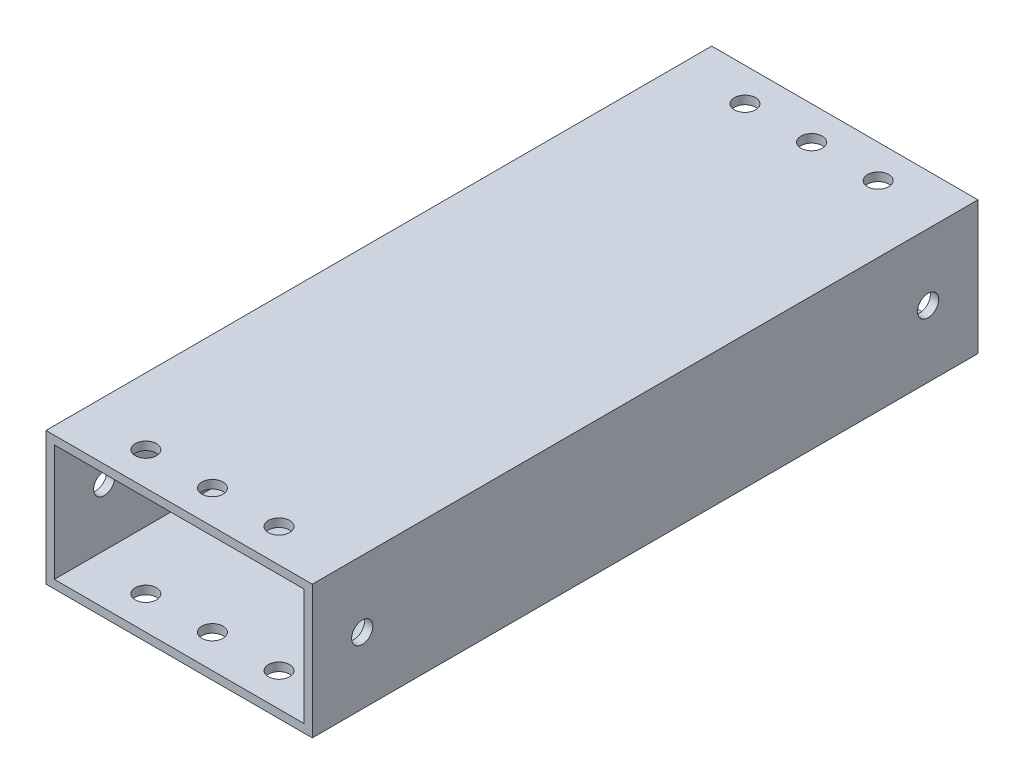
SolidWorks part; units mm, degrees
ref_plane "Front Plane" through (0, 0, 0) normal (0, 0, 1) x (1, 0, 0)
ref_plane "Top Plane" through (0, 0, 0) normal (0, 1, 0) x (1, 0, 0)
ref_plane "Right Plane" through (0, 0, 0) normal (1, 0, 0) x (0, 0, -1)
sketch "Sketch1" plane through (0, 0, 0) normal (0, 0, 1) x (1, 0, 0)
  line L0 (-23.8125, 11.1125) -> (23.8125, 11.1125)
  line L1 (-25.4, -12.7) -> (25.4, -12.7)
  line L2 (-25.4, -12.7) -> (-25.4, 12.7)
  line L3 (-25.4, 12.7) -> (25.4, 12.7)
  line L4 (25.4, -12.7) -> (25.4, 12.7)
  line L5 (-25.4, -12.7) -> (25.4, 12.7) construction
  line L6 (-25.4, 12.7) -> (25.4, -12.7) construction
  line L7 (23.8125, -11.1125) -> (23.8125, 11.1125)
  line L8 (-23.8125, -11.1125) -> (23.8125, -11.1125)
  line L9 (-23.8125, -11.1125) -> (-23.8125, 11.1125)
  point P0 (0, 0)
  dimension "D1" = 50.8
  dimension "D2" = 25.4
  dimension "D3" = 1.5875
extrude "Boss-Extrude1" add sketch "Sketch1" along normal mid plane 127
sketch "Sketch2" plane through (0, 12.7, 0) normal (0, 1, 0) x (1, 0, 0)
  line L0 (25.4, 63.5) -> (-25.4, 63.5) construction
  line L1 (25.4, 0) -> (-25.4, 0) construction
  line L2 (25.4, -63.5) -> (25.4, 63.5) construction
  line L3 (-25.4, -63.5) -> (-25.4, 63.5) construction
  circle A0 centre (-12.7, 57.15) radius 2.0193
  circle A1 centre (0, 57.15) radius 2.0193
  circle A2 centre (12.7, 57.15) radius 2.0193
  circle A3 centre (12.7, -57.15) radius 2.0193
  circle A4 centre (0, -57.15) radius 2.0193
  circle A5 centre (-12.7, -57.15) radius 2.0193
  dimension "D4" = 4.0386
  dimension "D1" = 12.7
  dimension "D2" = 12.7
  dimension "D3" = 6.35
extrude "Cut-Extrude1" cut sketch "Sketch2" against normal through all
sketch "Sketch3" plane through (-25.4, 0, 0) normal (-1, 0, 0) x (0, 0, 1)
  line L0 (-63.5, 12.7) -> (-63.5, -12.7) construction
  line L1 (0, 12.7) -> (0, -12.7) construction
  line L2 (63.5, 12.7) -> (-63.5, 12.7) construction
  line L3 (63.5, -12.7) -> (-63.5, -12.7) construction
  circle A0 centre (-53.975, 0) radius 2.0193
  circle A1 centre (53.975, 0) radius 2.0193
  dimension "D1" = 4.0386
  dimension "D2" = 9.525
extrude "Cut-Extrude2" cut sketch "Sketch3" against normal through all
